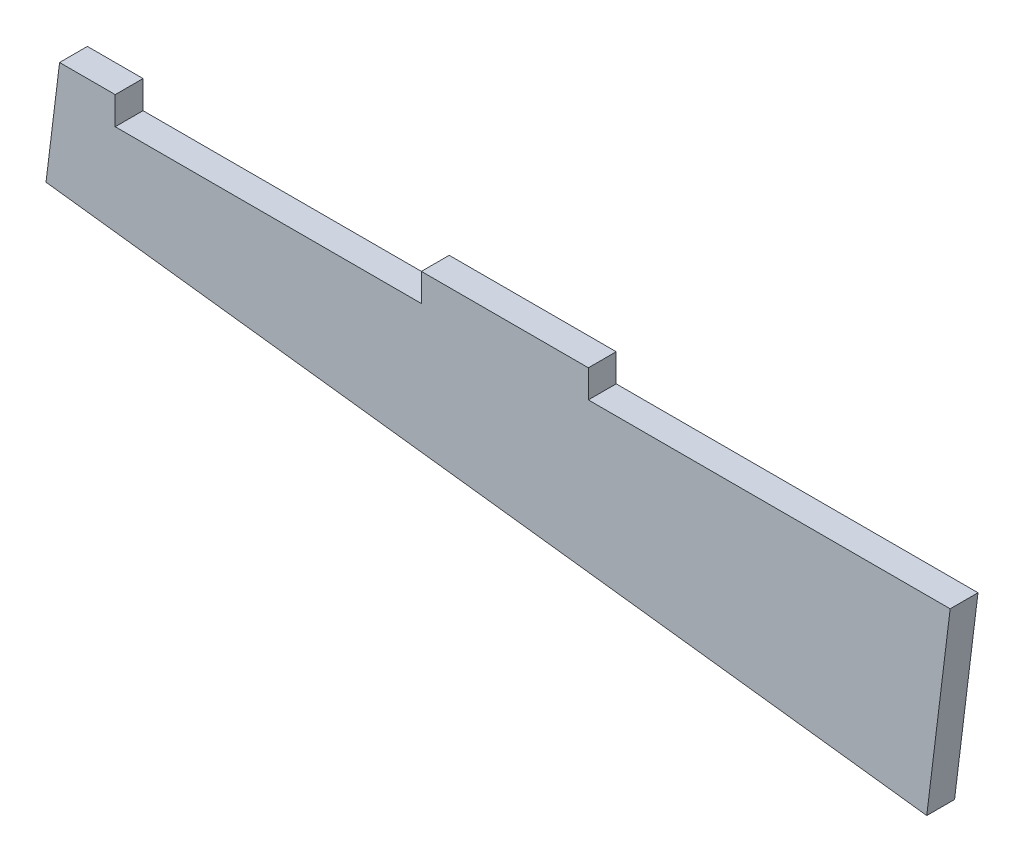
SolidWorks part; units mm, degrees
ref_plane "Front Plane" through (0, 0, 0) normal (0, 0, 1) x (1, 0, 0)
ref_plane "Top Plane" through (0, 0, 0) normal (0, 1, 0) x (1, 0, 0)
ref_plane "Right Plane" through (0, 0, 0) normal (1, 0, 0) x (0, 0, -1)
sketch "Sketch1" plane through (0, 0, 0) normal (0, 0, 1) x (1, 0, 0)
  line L0 (-195.3168, -62.6592) -> (-182.6168, -62.6592)
  line L4 (-182.6168, -62.6592) -> (-182.6168, -69.0092)
  line L5 (-182.6168, -69.0092) -> (-112.7668, -69.0092)
  line L6 (-112.7668, -69.0092) -> (-112.7668, -62.6592)
  line L7 (-112.7668, -62.6592) -> (-74.6668, -62.6592)
  line L8 (-74.6668, -62.6592) -> (-74.6668, -69.0092)
  line L9 (-74.6668, -69.0092) -> (7.8832, -69.0092)
  line L10 (7.8832, -69.0092) -> (2.5379, -112.5435)
  line L11 (2.5379, -112.5435) -> (-198.4122, -87.8699)
  line L12 (-198.4122, -87.8699) -> (-195.3168, -62.6592)
  line L13 (-1120.7888, 37.0793) -> (-727.0888, -11.261) construction
  dimension "D1" = 12.7
  dimension "D2" = 6.35
  dimension "D3" = 69.85
  dimension "D4" = 38.1
  dimension "D5" = 82.55
  dimension "D6" = 25.4
extrude "Boss-Extrude1" add sketch "Sketch1" against normal blind 6.35
